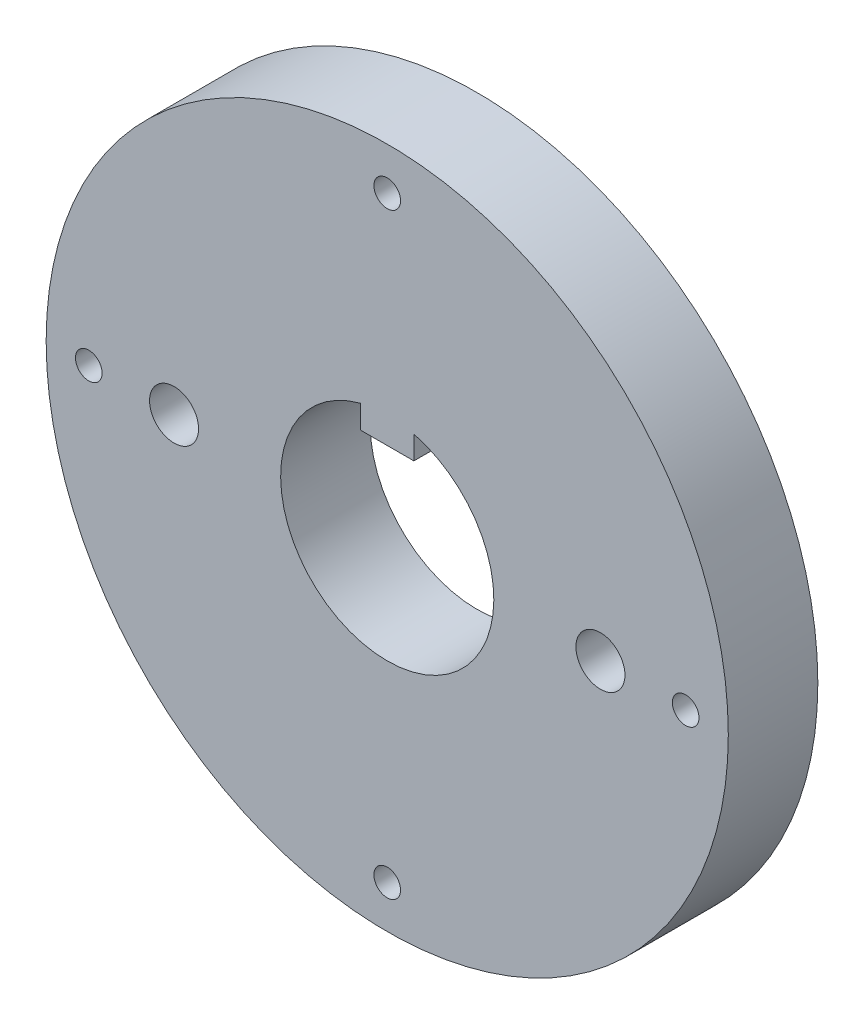
SolidWorks part; units mm, degrees
ref_plane "Front Plane" through (0, 0, 0) normal (0, 0, 1) x (1, 0, 0)
ref_plane "Top Plane" through (0, 0, 0) normal (0, 1, 0) x (1, 0, 0)
ref_plane "Right Plane" through (0, 0, 0) normal (1, 0, 0) x (0, 0, -1)
sketch "Sketch1" plane through (0, 0, 0) normal (0, 0, 1) x (1, 0, 0)
  circle A0 centre (0, 0) radius 20.32
  circle A1 centre (0, 0) radius 9.144
  dimension "D1" = 40.64
  dimension "D2" = 18.288
extrude "Boss-Extrude1" add sketch "Sketch1" along normal mid plane 5.334
sketch "Sketch2" plane through (0, 0, 2.667) normal (0, 0, 1) x (1, 0, 0)
  line L0 (0, 0) -> (12.7, 0) construction
  line L2 (0, 0) -> (-12.7, 0) construction
  circle A0 centre (12.7, 0) radius 1.4605
  circle A3 centre (-12.7, 0) radius 1.4605
  circle A6 centre (12.7, 0) radius 1.4605 [skipped]
  circle A7 centre (-12.7, 0) radius 1.4605 [skipped]
  dimension "D1" = 2.921
  dimension "D2" = 180
  dimension "D3" = 12.7
  dimension "D4" = 4
extrude "Cut-Extrude1" cut sketch "Sketch2" against normal through all
sketch "Sketch3" plane through (0, 0, 0) normal (0, 0, 1) x (1, 0, 0)
  line L1 (-1.5875, 6.35) -> (1.5875, 6.35)
  line L2 (-1.5875, 6.35) -> (-1.5875, 4.7625)
  line L3 (-1.5875, 4.7625) -> (1.5875, 4.7625)
  line L4 (1.5875, 6.35) -> (1.5875, 4.7625)
  circle A0 centre (0, 0) radius 9.525
  circle A1 centre (0, 0) radius 6.35
  point P8 (0, 4.7625)
  dimension "D1" = 19.05
  dimension "D2" = 12.7
  dimension "D3" = 1.5875
  dimension "D4" = 3.175
extrude "Boss-Extrude2" add sketch "Sketch3" along normal up to surface and the other way up to surface contours A0 A1 L2 L1 L4 | L4 A1 L2 L3 | A1 L1 L2 | A1 L4 L1 region at (-1.1919, 6.2897, 0) region at (1.1919, 6.2897, 0) region at (0, 5.524, 0) region at (-9.2556, 0, 0) up to face at (-11.2395, 0, 2.667) other way up to face at (-11.2395, 0, -2.667)
sketch "Sketch4" plane through (0, 0, 2.667) normal (0, 0, 1) x (1, 0, 0)
  line L0 (0, 0) -> (0, 17.78) construction
  circle A0 centre (0, 17.78) radius 0.7937
  circle A1 centre (17.78, 0) radius 0.7938
  circle A2 centre (0, -17.78) radius 0.7937
  circle A3 centre (-17.78, 0) radius 0.7937
  dimension "D1" = 1.5875
  dimension "D2" = 17.78
  dimension "D4" = 17.78
  dimension "D3" = 4
extrude "Cut-Extrude2" cut sketch "Sketch4" against normal through all
